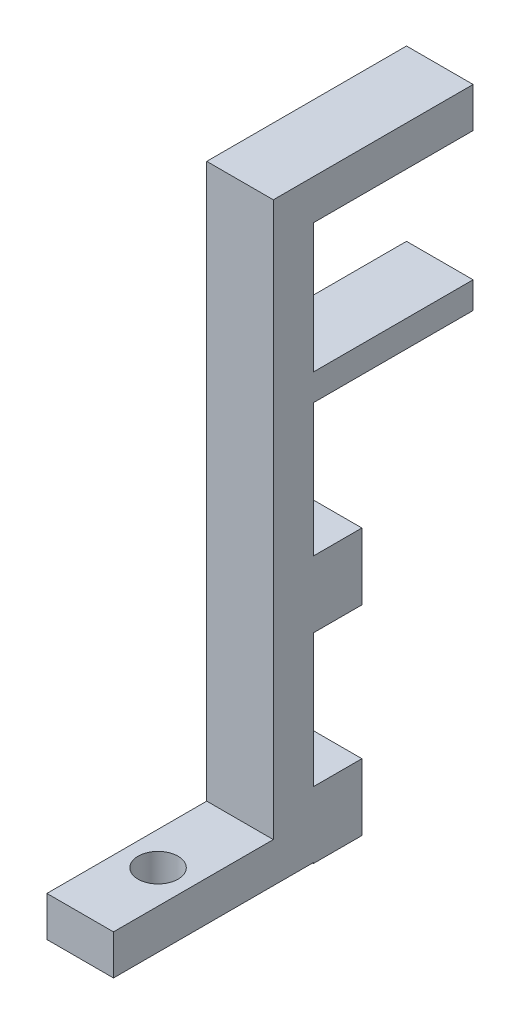
SolidWorks part; units mm, degrees
ref_plane "Front Plane" through (0, 0, 0) normal (0, 0, 1) x (1, 0, 0)
ref_plane "Top Plane" through (0, 0, 0) normal (0, 1, 0) x (1, 0, 0)
ref_plane "Right Plane" through (0, 0, 0) normal (1, 0, 0) x (0, 0, -1)
sketch "Sketch1" plane through (0, 0, 0) normal (0, 0, 1) x (1, 0, 0)
  line L1 (2.5, -19.3) -> (-2.5, -19.3)
  line L2 (2.5, -19.3) -> (2.5, 19.3)
  line L3 (2.5, 19.3) -> (-2.5, 19.3)
  line L4 (-2.5, -19.3) -> (-2.5, 19.3)
  line L5 (2.5, -19.3) -> (-2.5, 19.3) construction
  line L6 (2.5, 19.3) -> (-2.5, -19.3) construction
  point P0 (0, 0)
  dimension "D1" = 38.6
  dimension "D2" = 5
extrude "Boss-Extrude1" add sketch "Sketch1" along normal blind 3
sketch "Sketch3" plane through (0, -19.3, 0) normal (0, -1, 0) x (1, 0, 0)
  line L1 (-2.5, 0) -> (2.5, 0)
  line L2 (-2.5, 0) -> (-2.5, 15)
  line L3 (-2.5, 15) -> (2.5, 15)
  line L4 (2.5, 0) -> (2.5, 15)
  dimension "D1" = 15
  dimension "D2" = 5
extrude "Boss-Extrude2" add sketch "Sketch3" along normal blind 3
sketch "Sketch4" plane through (0, -19.3, 0) normal (0, 1, 0) x (1, 0, 0)
  line L0 (-2.5, -15) -> (-2.5, -3) construction
  line L1 (2.5, -3) -> (-2.5, -3) construction
  circle A0 centre (0, -9.1532) radius 1.5
  dimension "D1" = 3
  dimension "D2" = 2.5
  dimension "D3" = 6.1532
extrude "Cut-Extrude1" cut sketch "Sketch4" against normal blind 4
sketch "Sketch7" plane through (0, 19.3, 0) normal (0, 1, 0) x (1, 0, 0)
  line L1 (-2.5, -3) -> (2.5, -3)
  line L2 (-2.5, -3) -> (-2.5, 12)
  line L3 (-2.5, 12) -> (2.5, 12)
  line L4 (2.5, -3) -> (2.5, 12)
  dimension "D1" = 15
  dimension "D2" = 5
extrude "Boss-Extrude3" add sketch "Sketch7" along normal blind 3
sketch "Sketch8" plane through (0, 0, 0) normal (0, 0, -1) x (-1, 0, 0)
  line L0 (2.5, 19.3) -> (2.5, -22.3) construction
  line L1 (2.5, 7.6) -> (-2.5, 7.6)
  line L2 (2.5, 7.6) -> (2.5, 9.6)
  line L3 (2.5, 9.6) -> (-2.5, 9.6)
  line L4 (-2.5, 7.6) -> (-2.5, 9.6)
  line L5 (-2.5, -22.3) -> (-2.5, 19.3) construction
  line L7 (-2.5, 19.3) -> (2.5, 19.3) construction
  dimension "D1" = 9.7
  dimension "D2" = 2
extrude "Boss-Extrude4" add sketch "Sketch8" along normal blind 12
sketch "Sketch10" plane through (0, 0, 0) normal (0, 0, -1) x (-1, 0, 0)
  line L0 (-2.5, -22.3) -> (-2.5, 7.6) construction
  line L1 (-2.5, -2.3643) -> (2.5, -2.3643)
  line L2 (-2.5, -2.3643) -> (-2.5, -7.3643)
  line L3 (-2.5, -7.3643) -> (2.5, -7.3643)
  line L4 (2.5, -2.3643) -> (2.5, -7.3643)
  line L5 (2.5, 7.6) -> (2.5, -22.3) construction
  line L8 (-2.5, -17.3643) -> (2.5, -17.3643)
  line L9 (-2.5, -17.3643) -> (-2.5, -22.3643)
  line L10 (-2.5, -22.3643) -> (2.5, -22.3643)
  line L11 (2.5, -17.3643) -> (2.5, -22.3643)
  dimension "D1" = 5
  dimension "D2" = 10
  dimension "D4" = 5
extrude "Boss-Extrude5" add sketch "Sketch10" along normal blind 3.65
